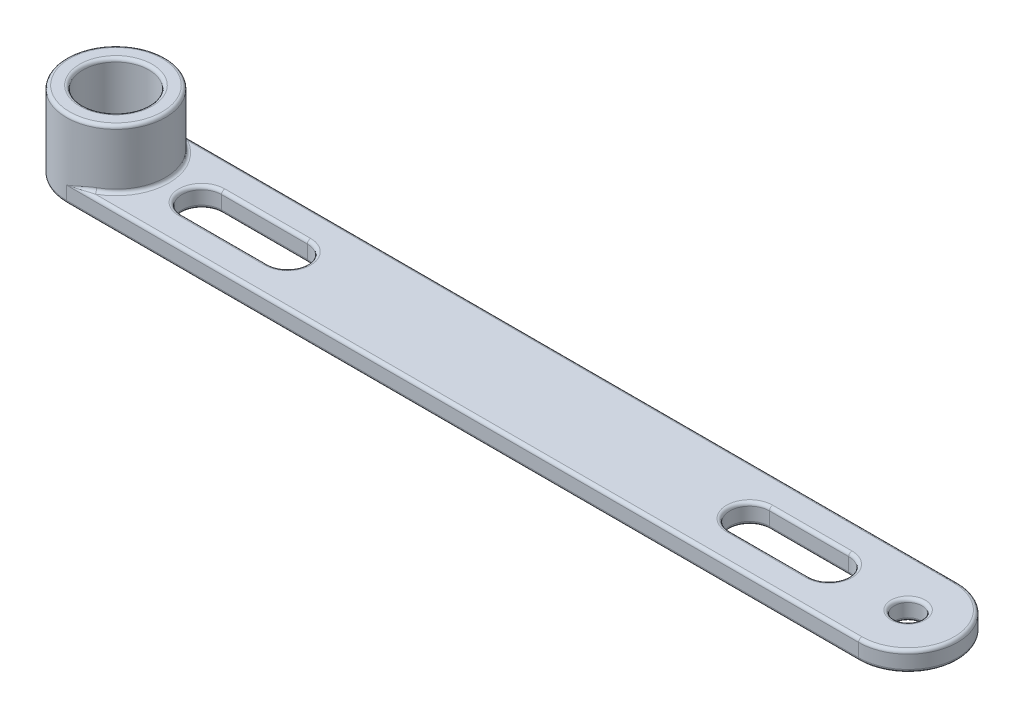
SolidWorks part; units mm, degrees
ref_plane "Front Plane" through (0, 0, 0) normal (0, 0, 1) x (1, 0, 0)
ref_plane "Top Plane" through (0, 0, 0) normal (0, 1, 0) x (1, 0, 0)
ref_plane "Right Plane" through (0, 0, 0) normal (1, 0, 0) x (0, 0, -1)
sketch "Sketch1" plane through (0, 0, 0) normal (0, 1, 0) x (1, 0, 0)
  line L0 (0, 7.5) -> (120, 7.5)
  line L1 (120, -7.5) -> (0, -7.5)
  circle A0 centre (0, 0) radius 2.1
  arc A1 (0, 7.5) -> (0, -7.5) centre (0, 0) ccw
  arc A2 (120, -7.5) -> (120, 7.5) centre (120, 0) ccw
  circle A3 centre (120, 0) radius 2.1
  dimension "D1" = 4.2
  dimension "D3" = 15
  dimension "D4" = 4.2
  dimension "D5" = 120
extrude "Boss-Extrude1" add sketch "Sketch1" along normal blind 3
sketch "Sketch2" plane through (0, 3, 0) normal (0, 1, 0) x (1, 0, 0)
  circle A0 centre (0, 0) radius 7.5
  circle A1 centre (0, 0) radius 5
  dimension "D1" = 15
  dimension "D2" = 10
extrude "Boss-Extrude2" add sketch "Sketch2" along normal blind 8.85
sketch "Sketch4" plane through (0, 3, 0) normal (0, 1, 0) x (1, 0, 0)
  line L0 (60, 7.5) -> (60, 17.7853) construction
  line L1 (120, 7.5) -> (0, 7.5) construction
  line L2 (108, 0) -> (96, 0) construction
  line L3 (108, -3) -> (96, -3)
  line L4 (108, 3) -> (96, 3)
  line L5 (13, 0) -> (26, 0) construction
  line L6 (13, 3) -> (26, 3)
  line L7 (13, -3) -> (26, -3)
  arc A0 (108, -3) -> (108, 3) centre (108, 0) ccw
  arc A1 (96, 3) -> (96, -3) centre (96, 0) ccw
  circle A2 centre (120, 0) radius 2.1 construction
  arc A3 (13, 3) -> (13, -3) centre (13, 0) ccw
  arc A4 (26, -3) -> (26, 3) centre (26, 0) ccw
  point P7 (102, 0)
  point P16 (19.5, 0)
  dimension "D3" = 3
  dimension "D4" = 3
  dimension "D1" = 12
  dimension "D2" = 12
  dimension "D5" = 13
  dimension "D6" = 13
extrude "Cut-Extrude1" cut sketch "Sketch4" against normal blind 6
fillet "Fillet1" radius 0.5 29 edges at (60, 3, -7.5) (127.5, 3, 0) (60, 0, -7.5) (127.5, 0, 0) (111, 0, 0) (102, 0, 3) (93, 0, 0) (111, 3, 0) (102, 3, 3) (93, 3, 0) (19.5, 0, 3) (10, 0, 0) (19.5, 0, -3) (19.5, 3, 3) (10, 3, 0) (19.5, 3, -3) (7.5, 3, 0) (-7.5, 0, 0) (60, 3, 7.5) (60, 0, 7.5) (0, 3, 5) (0, 11.85, 5) (120, 0, 2.1) (120, 3, 2.1) (102, 0, -3) (102, 3, -3) (29, 0, 0) (29, 3, 0) (0, 11.85, 7.5)
